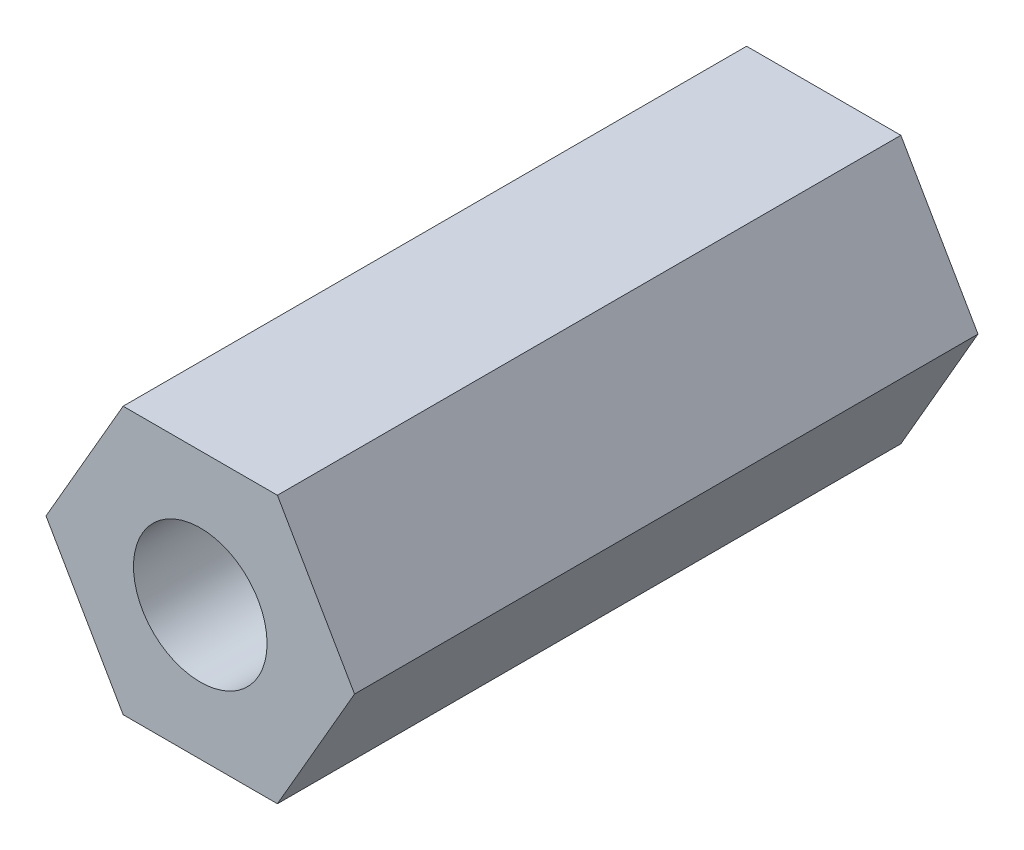
SolidWorks part; units mm, degrees
material "普通碳钢"
ref_plane "前视" through (0, 0, 0) normal (0, 0, 1) x (1, 0, 0)
ref_plane "上视" through (0, 0, 0) normal (0, 1, 0) x (1, 0, 0)
ref_plane "右视" through (0, 0, 0) normal (1, 0, 0) x (0, 0, -1)
sketch "草图1" plane through (0, 0, 0) normal (0, 0, 1) x (1, 0, 0)
  line L0 (0, 0) -> (3.4641, 0)
  line L1 (3.4641, 0) -> (5.1962, -3)
  line L2 (5.1962, -3) -> (3.4641, -6)
  line L3 (3.4641, -6) -> (0, -6)
  line L4 (0, -6) -> (-1.7321, -3)
  line L5 (-1.7321, -3) -> (0, 0)
  dimension "D1" = 6
  dimension "D2" = 6
extrude "凸台-拉伸1" add sketch "草图1" along normal blind 13
sketch "草图2" plane through (0, 0, 13) normal (0, 0, 1) x (1, 0, 0)
  line L0 (1.7321, 0) -> (1.7321, -6) construction
  line L1 (3.4641, 0) -> (0, 0) construction
  line L2 (0, -6) -> (3.4641, -6) construction
  line L3 (5.1962, -3) -> (-1.7321, -3) construction
  circle A0 centre (1.7321, -3) radius 1.5
extrude "切除-拉伸1" cut sketch "草图2" against normal through all
extrude "凸台-拉伸2" add sketch "草图1<2>" against normal blind 1
sketch "草图1<2>" plane through (0, 0, 0) normal (0, 0, 1) x (1, 0, 0) same geometry as "草图1"
extrude "切除-拉伸2" cut sketch "草图2<2>" against normal blind 14
sketch "草图2<2>" plane through (0, 0, 13) normal (0, 0, 1) x (1, 0, 0) same geometry as "草图2"
